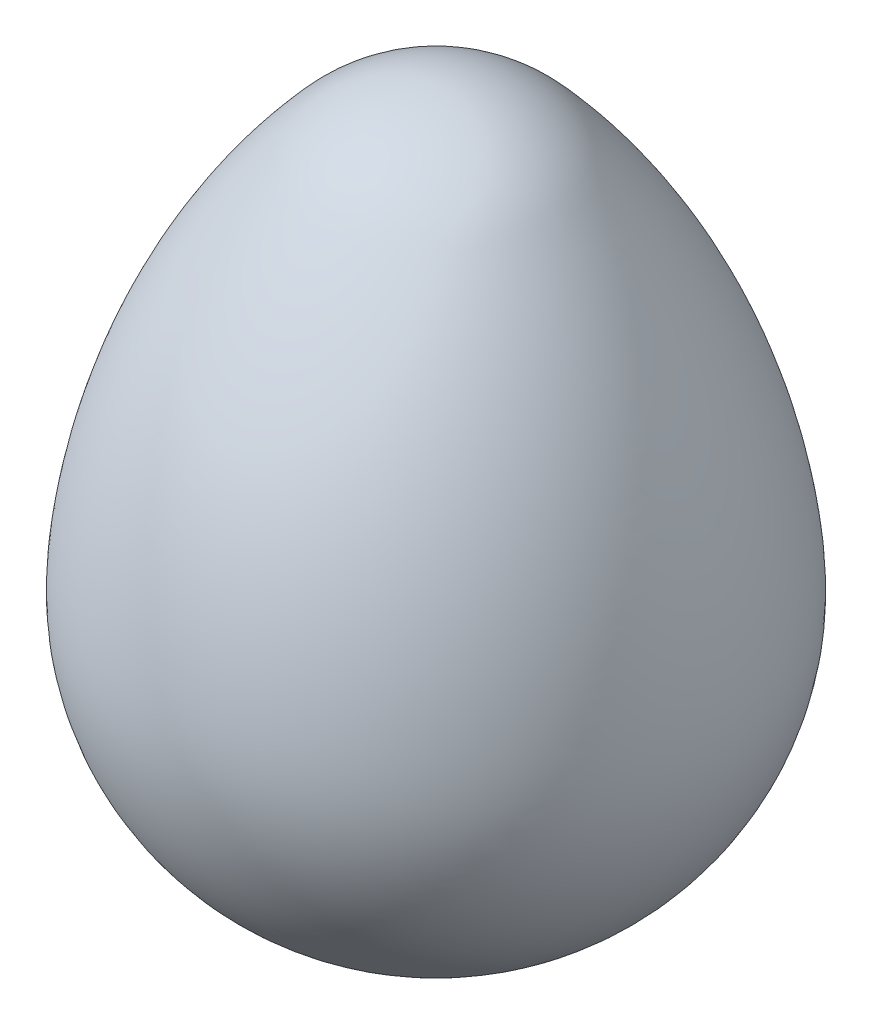
SolidWorks part; units mm, degrees
ref_plane "Front Plane" through (0, 0, 0) normal (0, 0, 1) x (1, 0, 0)
ref_plane "Top Plane" through (0, 0, 0) normal (0, 1, 0) x (1, 0, 0)
ref_plane "Right Plane" through (0, 0, 0) normal (1, 0, 0) x (0, 0, -1)
sketch "Sketch1" plane through (0, 0, 0) normal (0, 0, 1) x (1, 0, 0)
  line L15 (0, 27.5) -> (0, -17.5)
  line L16 (0, 0) -> (0, 35.011) construction
  arc A0 (0, -17.5) -> (17.3939, 1.9241) centre (0, 0) ccw construction
  arc A1 (17.3939, 1.9241) -> (7.5, 24.1376) centre (-22.3636, -2.4738) ccw construction
  arc A2 (7.5, 24.1376) -> (0, 27.5) centre (0, 17.4543) ccw construction
  spline S0 degree 3 poles (0, 27.5) (2.153, 27.5) (4.1993, 26.8307) (5.9361, 25.5585) (6.3143, 25.2815) (7.0318, 24.6746) (7.9731, 23.6095) (8.5718, 22.8879) (8.8648, 22.522) (12.3084, 18.2197) (14.8032, 13.306) (16.2443, 7.987) (16.6318, 6.5571) (17.2478, 3.6542) (17.6633, -0.9924) (17.1175, -3.9289) (16.6655, -5.3397) (14.2588, -12.8509) (7.8873, -17.5) (0, -17.5) knots 0 0 0 0 0.102843 0.102843 0.102843 0.125999 0.149155 0.172311 0.172311 0.172311 0.440734 0.440734 0.440734 0.513919 0.587104 0.660289 0.660289 0.660289 1 1 1 1 weights 1 0.966971 0.966971 1 1 1 1 1 1 0.986013 0.986013 1 1 1 1 1 1 0.871876 0.871876 1
  dimension "D1" = 35
  dimension "D2" = 45
  dimension "D4" = 40
  dimension "D3" = 15
revolve "Revolve1" add sketch "Sketch1" angle 360 about L16
